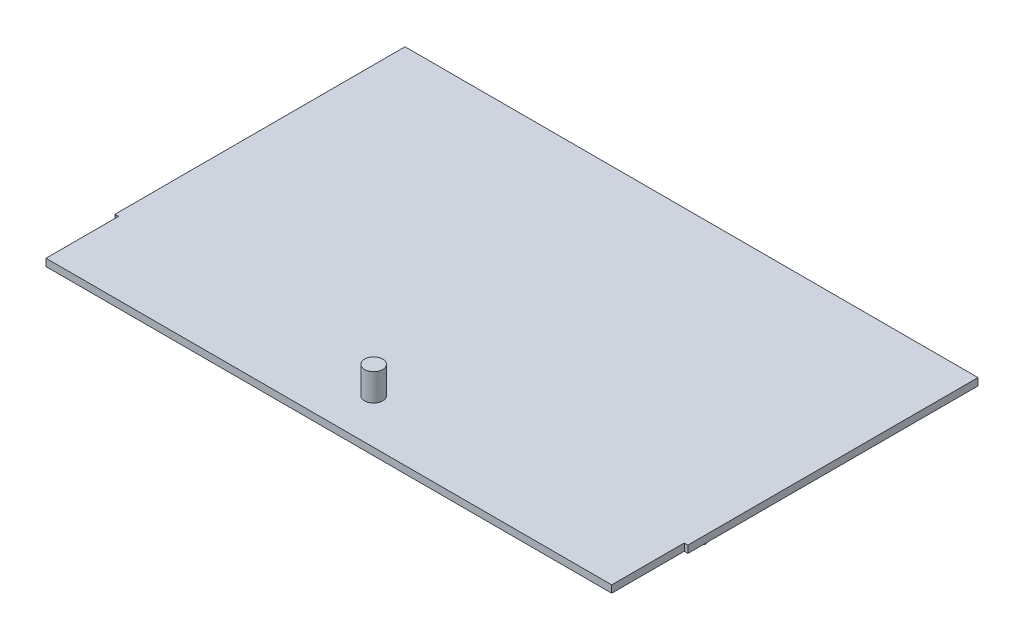
SolidWorks part; units mm, degrees
ref_plane "Front Plane" through (0, 0, 0) normal (0, 0, 1) x (1, 0, 0)
ref_plane "Top Plane" through (0, 0, 0) normal (0, 1, 0) x (1, 0, 0)
ref_plane "Right Plane" through (0, 0, 0) normal (1, 0, 0) x (0, 0, -1)
sketch "Sketch1" plane through (0, 0, 0) normal (0, 1, 0) x (1, 0, 0)
  line L0 (-5.476, 107.7101) -> (-5.476, 27.7101)
  line L1 (-5.476, 107.7101) -> (152.524, 107.7101)
  line L3 (-4.476, 7.7101) -> (151.524, 7.7101)
  line L4 (152.524, 107.7101) -> (152.524, 27.7101)
  line L5 (-5.476, 27.7101) -> (-4.476, 27.7101)
  line L6 (-4.476, 27.7101) -> (-4.476, 7.7101)
  line L8 (152.524, 27.7101) -> (151.524, 27.7101)
  line L9 (151.524, 27.7101) -> (151.524, 7.7101)
  dimension "D1" = 158
  dimension "D2" = 80
  dimension "D3" = 80
  dimension "D4" = 1
  dimension "D5" = 1
  dimension "D6" = 20
extrude "Boss-Extrude1" add sketch "Sketch1" along normal blind 2
sketch "Sketch2" plane through (0, 2, 0) normal (0, 1, 0) x (1, 0, 0)
  line L0 (73.524, 7.7101) -> (73.524, 20.0583) construction
  line L1 (-4.476, 7.7101) -> (151.524, 7.7101) construction
  circle A0 centre (73.524, 20.0583) radius 2.5
  dimension "D1" = 5
extrude "Boss-Extrude2" add sketch "Sketch2" along normal blind 7.5
sketch "Sketch4" plane through (0, 0, 0) normal (0, -1, 0) x (1, 0, 0)
  line L1 (-5.476, -31.0337) -> (-4.476, -31.0337)
  line L2 (-5.476, -31.0337) -> (-4.476, -31.0337)
  arc A1 (-4.476, -31.0337) -> (-5.476, -31.0337) centre (-4.976, -31.0337) ccw
  arc A2 (-4.476, -31.0337) -> (-5.476, -31.0337) centre (-4.976, -31.0337) ccw
  dimension "D1" = 0
revolve "Revolve3" add sketch "Sketch4" angle 360 about L2
sketch "Sketch7" plane through (0, 0, 0) normal (0, -1, 0) x (1, 0, 0)
  line L0 (152.024, -32.7101) -> (152.0487, -32.2107) construction
  line L1 (152.024, -32.7101) -> (151.9992, -33.2095) construction
  line L2 (152.024, -32.7101) -> (152.0487, -32.2107)
  line L3 (152.024, -32.7101) -> (151.9992, -33.2095)
  arc A0 (152.0487, -32.2107) -> (151.9992, -33.2095) centre (152.024, -32.7101) ccw construction
  arc A1 (152.0487, -32.2107) -> (151.9992, -33.2095) centre (152.024, -32.7101) ccw
revolve "Revolve4" add sketch "Sketch7" angle 360 about L3
